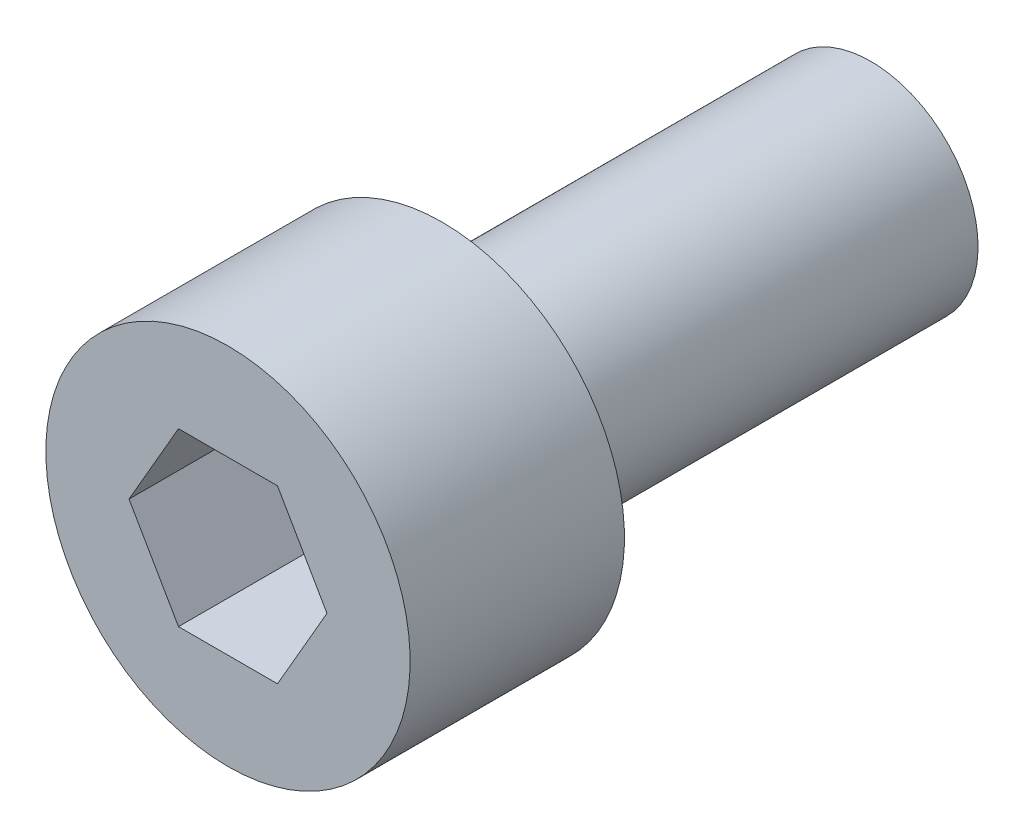
SolidWorks part; units mm, degrees
material "AISI 304"
ref_plane "Front Plane" through (0, 0, 0) normal (0, 0, 1) x (1, 0, 0)
ref_plane "Top Plane" through (0, 0, 0) normal (0, 1, 0) x (1, 0, 0)
ref_plane "Right Plane" through (0, 0, 0) normal (1, 0, 0) x (0, 0, -1)
ref_axis "Axis1" through (0, 0, -52.8182) along (0, 0, 1)
ref_axis "Axis2" through (0, -15.5981, 0) along (0, 1, 0)
ref_axis "Axis3" through (-12.2581, 0, 0) along (1, 0, 0)
sketch "Sketch1" plane through (0, 0, 0) normal (1, 0, 0) x (0, 0, -1)
  line L0 (-5, 0) -> (-5, 4.25)
  line L1 (-5, 4.25) -> (0, 4.25)
  line L2 (0, 4.25) -> (0, 2.5)
  line L3 (0, 2.5) -> (10, 2.5)
  line L4 (10, 2.5) -> (10, 0)
  line L5 (10, 0) -> (-5, 0)
  line L6 (-5.5849, 0) -> (13.8966, 0) construction
  dimension "D1" = 5
  dimension "D2" = 8.5
  dimension "D3" = 5
  dimension "Length" = 10
revolve "Revolve1" add sketch "Sketch1" angle 360 about L6
cosmetic thread "Cosmetic Thread1" parameters "D1"=10, "D2"=0
sketch "Sketch2" plane through (0, 0, 5) normal (0, 0, 1) x (1, 0, 0)
  line L1 (1.1547, -2) -> (2.3094, 0)
  line L2 (2.3094, 0) -> (1.1547, 2)
  line L3 (1.1547, 2) -> (-1.1547, 2)
  line L4 (-1.1547, 2) -> (-2.3094, 0)
  line L5 (-2.3094, 0) -> (-1.1547, -2)
  line L6 (-1.1547, -2) -> (1.1547, -2)
  circle A0 centre (0, 0) radius 2 construction
  dimension "D1" = 4
extrude "Cut-Extrude1" cut sketch "Sketch2" against normal blind 3
